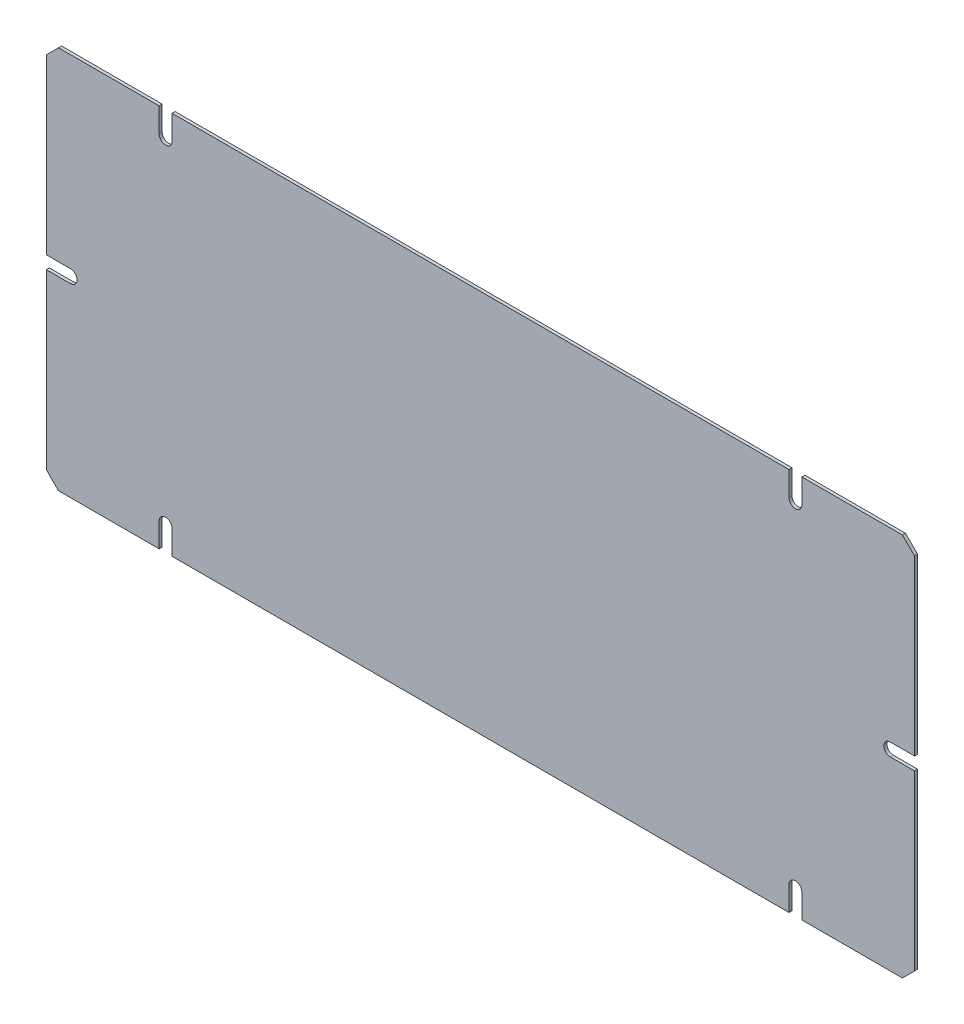
SolidWorks part; units mm, degrees
material "PE High Density"
ref_plane "Front" through (0, 0, 0) normal (0, 0, 1) x (1, 0, 0)
ref_plane "Top" through (0, 0, 0) normal (0, 1, 0) x (1, 0, 0)
ref_plane "Right" through (0, 0, 0) normal (1, 0, 0) x (0, 0, -1)
ref_axis "Axis1" through (0, 0, 55) along (0, 0, -1)
sketch "Sketch1" plane through (0, 0, 0) normal (0, 0, 1) x (1, 0, 0)
  line L1 (-227.584, 100.584) -> (227.584, 100.584)
  line L2 (-227.584, 100.584) -> (-227.584, -100.584)
  line L3 (-227.584, -100.584) -> (227.584, -100.584)
  line L4 (227.584, 100.584) -> (227.584, -100.584)
  line L5 (-227.584, 100.584) -> (227.584, -100.584) construction
  line L6 (-227.584, -100.584) -> (227.584, 100.584) construction
  point P0 (0, 0)
  dimension "D1" = 201.168
  dimension "D2" = 455.168
extrude "Boss-Extrude1" add sketch "Sketch1" along normal blind 1.5875
hole_wizard "1/4 Clearance Hole1" positions "Sketch2" profile "Sketch3" hole size "1/4" standard "ANSI Inch" end condition up to next
sketch "Sketch2" plane through (0, 0, 1.5875) normal (0, 0, 1) x (1, 0, 0)
  line L2 (-214.884, 87.884) -> (214.884, 87.884) construction
  line L3 (-214.884, 87.884) -> (-214.884, -87.884) construction
  line L4 (-214.884, -87.884) -> (214.884, -87.884) construction
  line L5 (214.884, 87.884) -> (214.884, -87.884) construction
  line L6 (-214.884, 87.884) -> (214.884, -87.884) construction
  line L7 (-214.884, -87.884) -> (214.884, 87.884) construction
  line L8 (-227.584, 100.584) -> (-227.584, -100.584) construction
  line L9 (227.584, 100.584) -> (-227.584, 100.584) construction
  line L10 (-227.584, -100.584) -> (227.584, -100.584) construction
  line L11 (227.584, -100.584) -> (227.584, 100.584) construction
  line L12 (-214.884, 0) -> (214.884, 0) construction
  line L14 (0, 87.884) -> (0, -87.884) construction
  line L15 (-165.1, 87.884) -> (-165.1, -87.884) construction
  line L17 (165.1, 87.884) -> (165.1, -87.884) construction
  point P0 (-165.1, 87.884)
  point P2 (165.1, 87.884)
  point P4 (214.884, 0)
  point P6 (-214.884, 0)
  point P8 (-165.1, -87.884)
  point P10 (165.1, -87.884)
  point P224 (214.884, 0)
  dimension "D1" = 12.7
  dimension "D2" = 12.7
  dimension "D3" = 12.7
  dimension "D4" = 12.7
  dimension "D5" = 330.2
sketch "Sketch3" plane through (-165.1, 87.884, 1.5875) normal (1, 0, 0) x (0, -1, 0)
  line L0 (0, 0) -> (0, 1.5875)
  line L1 (0, 1.5875) -> (3.3782, 1.5875)
  line L2 (3.3782, 1.5875) -> (3.3782, 0)
  line L5 (3.3782, 0) -> (0, 0)
  line L11 (0, -6.35) -> (0, 107.95) construction
  dimension "Thru Hole Dia." = 6.7564
  dimension "Thru Hole Depth" = 1.5875
chamfer "Chamfer1" distance 6.35 angle 45 4 edges at (-227.584, -100.584, 0.7937) (-227.584, 100.584, 0.7937) (227.584, -100.584, 0.7937) (227.584, 100.584, 0.7937)
sketch "Sketch4" plane through (0, 0, 1.5875) normal (0, 0, 1) x (1, 0, 0)
  line L0 (-165.1, 91.2622) -> (-165.1, 84.5058) construction
  line L1 (-168.4782, 87.884) -> (-161.7218, 87.884)
  line L2 (-168.4782, 87.884) -> (-168.4782, 102.3726)
  line L3 (-168.4782, 102.3726) -> (-161.7218, 102.3726)
  line L4 (-161.7218, 87.884) -> (-161.7218, 102.3726)
  line L5 (-168.4782, 87.884) -> (-161.7218, 102.3726) construction
  line L6 (-168.4782, 102.3726) -> (-161.7218, 87.884) construction
  line L7 (165.1, 91.2622) -> (165.1, 84.5058) construction
  line L8 (161.7218, 87.884) -> (168.4782, 87.884)
  line L9 (161.7218, 87.884) -> (161.7218, 102.3726)
  line L10 (161.7218, 102.3726) -> (168.4782, 102.3726)
  line L11 (168.4782, 87.884) -> (168.4782, 102.3726)
  line L12 (161.7218, 87.884) -> (168.4782, 102.3726) construction
  line L13 (161.7218, 102.3726) -> (168.4782, 87.884) construction
  line L14 (-218.2622, 0) -> (-211.5058, 0) construction
  line L15 (-214.884, 3.3782) -> (-229.3726, 3.3782) construction
  line L16 (-214.884, 3.3782) -> (-214.884, -3.3782) construction
  line L17 (-214.884, -3.3782) -> (-229.3726, -3.3782) construction
  line L18 (-229.3726, 3.3782) -> (-229.3726, -3.3782) construction
  line L19 (-214.884, 3.3782) -> (-229.3726, -3.3782) construction
  line L20 (-214.884, -3.3782) -> (-229.3726, 3.3782) construction
  circle A0 centre (-165.1, 87.884) radius 3.3782 construction
  circle A1 centre (165.1, 87.884) radius 3.3782 construction
  circle A2 centre (-214.884, 0) radius 3.3782 construction
  point P4 (-165.1, 95.1283)
  point P7 (-165.1, 87.884)
  point P15 (165.1, 95.1283)
  point P18 (165.1, 87.884)
  point P26 (-222.1283, 0)
  point P29 (-214.884, 0)
  dimension "D1" = 14.4886
extrude "Cut-Extrude1" cut sketch "Sketch4" against normal up to next
mirror "Mirror5" about plane through (0, 0, 0) normal (0, 1, 0) of "Cut-Extrude1"
sketch "Sketch5" plane through (0, 0, 1.5875) normal (0, 0, 1) x (1, 0, 0)
  line L0 (-218.2622, 0) -> (-211.5058, 0) construction
  line L1 (-214.884, 3.3782) -> (-233.934, 3.3782)
  line L2 (-214.884, 3.3782) -> (-214.884, -3.3782)
  line L3 (-214.884, -3.3782) -> (-233.934, -3.3782)
  line L4 (-233.934, 3.3782) -> (-233.934, -3.3782)
  line L5 (-214.884, 3.3782) -> (-233.934, -3.3782) construction
  line L6 (-214.884, -3.3782) -> (-233.934, 3.3782) construction
  circle A0 centre (-214.884, 0) radius 3.3782 construction
  point P4 (-224.409, 0)
  point P7 (-214.884, 0)
  dimension "D1" = 19.05
extrude "Cut-Extrude2" cut sketch "Sketch5" against normal up to next
mirror "Mirror6" about plane through (0, 0, 0) normal (1, 0, 0) of "Cut-Extrude2"
